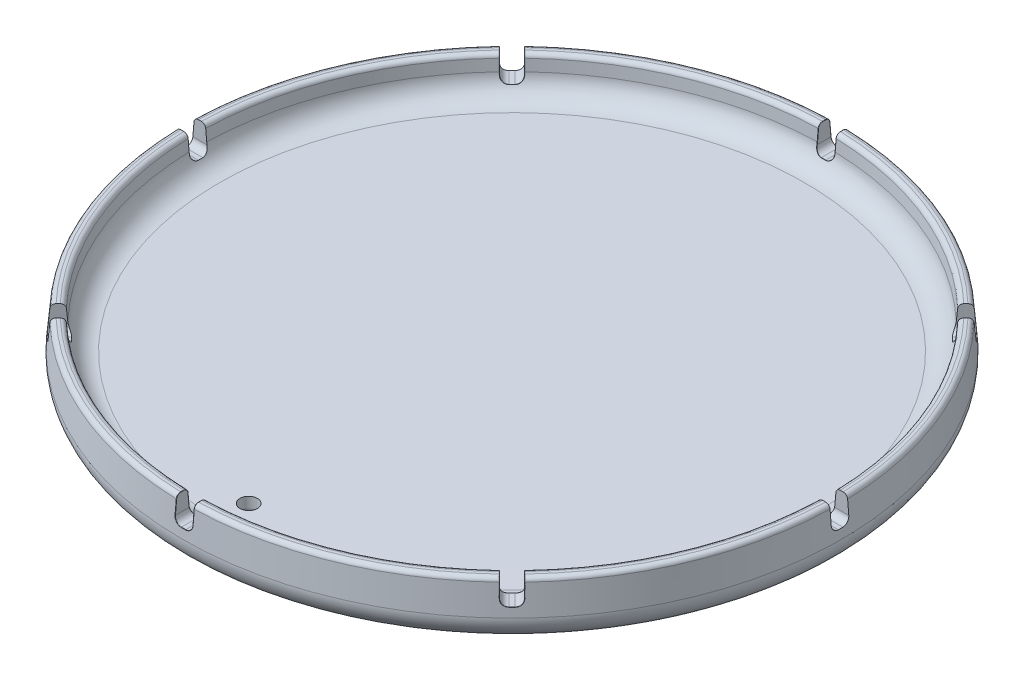
SolidWorks part; units mm, degrees
ref_plane "Front Plane" through (0, 0, 0) normal (0, 0, 1) x (1, 0, 0)
ref_plane "Top Plane" through (0, 0, 0) normal (0, 1, 0) x (1, 0, 0)
ref_plane "Right Plane" through (0, 0, 0) normal (1, 0, 0) x (0, 0, -1)
sketch "Sketch1" plane through (0, 0, 0) normal (0, 1, 0) x (1, 0, 0)
  circle A0 centre (0, 0) radius 47.244
  dimension "D1" = 94.488
extrude "Boss-Extrude1" add sketch "Sketch1" along normal blind 3.175
fillet "Fillet1" [suppressed] radius 1.905
sketch "Sketch2" plane through (0, 3.175, 0) normal (0, 1, 0) x (1, 0, 0)
  circle A0 centre (0, 0) radius 47.244
  circle A1 centre (0, 0) radius 45.6565
  dimension "D1" = 94.488
  dimension "D2" = 1.5875
extrude "Boss-Extrude2" add sketch "Sketch2" along normal blind 5.08
draft "Draft1" type of draft neutral plane draft angle 5 faces to draft 2 face at (0, 8.255, 45.6565) face at (0, 0, 47.244) neutral plane through (0, 8.255, 0) neutral plane normal (0, 1, 0) parameters "D1"=5
fillet "Fillet2" radius 3.175 1 edges at (0, 3.175, 45.2121)
fillet "Fillet3" radius 0.635 2 edges at (0, 8.255, 45.6565) (0, 8.255, 47.244)
sketch "Sketch3" plane through (0, 3.175, 0) normal (0, 1, 0) x (1, 0, 0)
  line L1 (-1.27, -49.5146) -> (1.27, -49.5146)
  line L2 (-1.27, -49.5146) -> (-1.27, 49.5146)
  line L3 (-1.27, 49.5146) -> (1.27, 49.5146)
  line L4 (1.27, -49.5146) -> (1.27, 49.5146)
  line L5 (-1.27, -49.5146) -> (1.27, 49.5146) construction
  line L6 (-1.27, 49.5146) -> (1.27, -49.5146) construction
  point P0 (0, 0)
  dimension "D1" = 2.54
extrude "Cut-Extrude1" cut sketch "Sketch3" along normal through all from offset 1.5875
pattern_circular "CirPattern1" count 8 over 360 about axis through (0, 0, 0) along (0, 1, 0) of "Cut-Extrude1"
fillet "Fillet4" radius 0.9525 12 edges at (1.27, 4.7625, 46.2835) (1.27, 4.7625, -46.2835) (-1.27, 4.7625, 46.2835) (-1.27, 4.7625, -46.2835) (33.6254, 4.7625, 31.8294) (-31.8294, 4.7625, -33.6254) (31.8294, 4.7625, 33.6254) (-33.6254, 4.7625, -31.8294) (46.2835, 4.7625, -1.27) (46.2835, 4.7625, 1.27) (31.8294, 4.7625, -33.6254) (33.6254, 4.7625, -31.8294)
fillet "Fillet5" radius 0.0397 72 edges at (34.112, 8.1645, 32.3159) (32.41, 8.0582, 34.206) (-32.41, 8.0582, -34.206) (-34.112, 8.1645, -32.3159) (33.731, 8.255, 31.935) (31.935, 8.255, 33.731) (-33.731, 8.255, -31.935) (-31.935, 8.255, -33.731) (-1.27, 7.0772, 46.5505) (-1.27, 7.2172, -46.712) (1.27, 7.1581, 46.6568) (1.27, 7.1236, -46.6171) (0, 4.7625, 45.0523) (0, 4.7625, 47.5496) (-31.8568, 4.7625, -31.8568) (-33.6226, 4.7625, -33.6226) (0, 4.7625, -45.0523) (0, 4.7625, -47.5496) (31.8568, 4.7625, 31.8568) (33.6226, 4.7625, 33.6226) (0.8647, 4.9353, 45.1368) (1.0597, 5.118, 47.5066) (-0.9102, 4.9694, 47.5227) (-1.0579, 5.1158, 45.2156) (-32.96, 4.9694, -34.2473) (-31.2242, 5.1158, -32.7203) (-32.528, 4.9353, -31.3052) (-34.3416, 5.118, -32.843) (0.9102, 4.9694, -47.5227) (1.0579, 5.1158, -45.2156) (-0.8647, 4.9353, -45.1368) (-1.0597, 5.118, -47.5066) (32.528, 4.9353, 31.3052) (34.3416, 5.118, 32.843) (32.96, 4.9694, 34.2473) (31.2242, 5.1158, 32.7203) (1.27, 7.1343, -46.2356) (1.27, 8.1409, 47.0081) (-1.27, 7.1899, -46.1775) (-1.27, 8.0534, 47.1091) (-1.27, 8.255, -46.4329) (1.27, 8.255, -46.4329) (1.27, 8.255, 46.4329) (-1.27, 8.255, 46.4329) (-33.256, 8.0581, -31.46) (-31.554, 8.1645, -33.3501) (31.554, 8.1645, 33.3501) (33.256, 8.0581, 31.46)
sketch "Sketch4" plane through (0, 3.175, 0) normal (0, 1, 0) x (1, 0, 0)
  circle A0 centre (0, 0) radius 34.925
  dimension "D1" = 69.85
extrude "Cut-Extrude2" [suppressed] cut sketch "Sketch4" against normal through all
fillet "Fillet7" [suppressed] radius 1.905
sketch "Sketch5" plane through (0, 0, 0) normal (0, -1, 0) x (1, 0, 0)
  circle A0 centre (0, 38.1) radius 1.27
  dimension "D2" = 2.54
  dimension "D1" = 38.1
extrude "Cut-Extrude3" cut sketch "Sketch5" against normal through all
fillet "Fillet9" radius 3.175 1 edges at (0, 0, 47.9662)
fillet "Fillet10" radius 1.5875 1 edges at (0, 0, 36.83)
